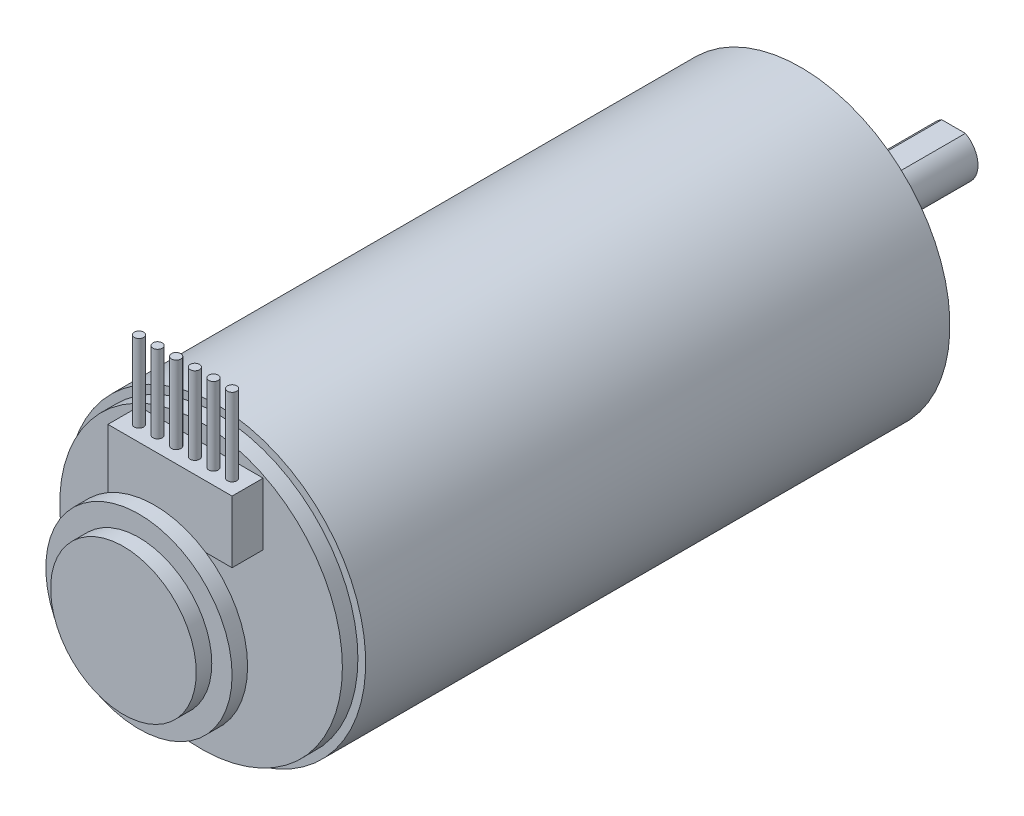
SolidWorks part; units mm, degrees
ref_plane "Front Plane" through (0, 0, 0) normal (0, 0, 1) x (1, 0, 0)
ref_plane "Top Plane" through (0, 0, 0) normal (0, 1, 0) x (1, 0, 0)
ref_plane "Right Plane" through (0, 0, 0) normal (1, 0, 0) x (0, 0, -1)
sketch "Sketch1" plane through (0, 0, 0) normal (0, 0, 1) x (1, 0, 0)
  circle A0 centre (0, 0) radius 2
  dimension "D1" = 4
extrude "Boss-Extrude1" add sketch "Sketch1" along normal blind 10
sketch "Sketch2" plane through (0, 0, 10) normal (0, 0, 1) x (1, 0, 0)
  circle A0 centre (0, 0) radius 3.5
  dimension "D1" = 7
extrude "Boss-Extrude2" add sketch "Sketch2" along normal blind 2.5
sketch "Sketch3" plane through (0, 0, 0) normal (0, 0, -1) x (-1, 0, 0)
  line L0 (0, 0) -> (0, 2) construction
  line L1 (-3.6247, 2.512) -> (3.6247, 2.512)
  line L2 (-3.6247, 2.512) -> (-3.6247, 1.75)
  line L3 (-3.6247, 1.75) -> (3.6247, 1.75)
  line L4 (3.6247, 2.512) -> (3.6247, 1.75)
  circle A1 centre (0, 0) radius 2 construction
  point P10 (0, 1.75)
  dimension "D1" = 1.75
  dimension "D2" = 0.762
  dimension "D3" = 3.6247
extrude "Cut-Extrude1" cut sketch "Sketch3" against normal blind 8
sketch "Sketch4" plane through (0, 0, 12.5) normal (0, 0, 1) x (1, 0, 0)
  circle A0 centre (0, 0) radius 12.2
  dimension "D1" = 24.4
extrude "Boss-Extrude3" add sketch "Sketch4" along normal blind 47.8
sketch "Sketch5" plane through (0, 0, 60.3) normal (0, 0, 1) x (1, 0, 0)
  circle A0 centre (0, 0) radius 11.565
  circle A1 centre (0, 0) radius 12.2 construction
  dimension "D1" = 0.635
extrude "Boss-Extrude4" add sketch "Sketch5" along normal blind 1.27
sketch "Sketch6" plane through (0, 0, 0) normal (0, 1, 0) x (1, 0, 0)
  line L0 (-11.565, -61.57) -> (11.565, -61.57) construction
  line L1 (-11.565, -61.57) -> (11.565, -61.57) construction
  line L3 (-5.08, -61.57) -> (5.08, -61.57)
  line L4 (-5.08, -61.57) -> (-5.08, -64.11)
  line L5 (-5.08, -64.11) -> (5.08, -64.11)
  line L6 (5.08, -61.57) -> (5.08, -64.11)
  point P6 (0, -61.57)
  point P7 (0, -61.57)
  point P8 (0, -61.57)
  dimension "D1" = 2.54
  dimension "D2" = 5.08
  dimension "D3" = 5.08
  dimension "D4" = 5.08
  dimension "D5" = 5.08
extrude "Boss-Extrude5" add sketch "Sketch6" along normal blind 5.08 from offset 5.08
sketch "Sketch8" plane through (0, 0, 61.57) normal (0, 0, 1) x (1, 0, 0)
  circle A0 centre (0, 0) radius 1.27
  dimension "D1" = 2.54
extrude "Boss-Extrude8" add sketch "Sketch8" along normal blind 3.81
sketch "Sketch9" plane through (0, 0, 65.38) normal (0, 0, 1) x (1, 0, 0)
  circle A0 centre (0, 0) radius 7.62
  dimension "D1" = 15.24
extrude "Boss-Extrude9" add sketch "Sketch9" along normal blind 1.27
sketch "Sketch10" plane through (0, 0, 66.65) normal (0, 0, 1) x (1, 0, 0)
  circle A0 centre (0, 0) radius 5.9577
extrude "Boss-Extrude10" add sketch "Sketch10" along normal blind 1.27
sketch "Sketch11" plane through (0, 10.16, 0) normal (0, 1, 0) x (1, 0, 0)
  line L0 (-5.08, -62.84) -> (5.08, -62.84) construction
  line L1 (-5.08, -61.57) -> (-5.08, -64.11) construction
  line L2 (5.08, -64.11) -> (5.08, -61.57) construction
  line L3 (0, -62.84) -> (-2.0643, -62.84) construction
  line L4 (-2.0643, -62.84) -> (-4.2233, -62.84) construction
  line L5 (0, -62.84) -> (2.159, -62.84) construction
  line L6 (2.159, -62.84) -> (4.318, -62.84) construction
  line L7 (0, -61.57) -> (0, -64.11) construction
  line L8 (5.08, -61.57) -> (-5.08, -61.57) construction
  line L9 (-5.08, -64.11) -> (5.08, -64.11) construction
  circle A0 centre (-0.762, -62.84) radius 0.381
  circle A1 centre (-2.286, -62.84) radius 0.381
  circle A2 centre (-3.81, -62.84) radius 0.381
  circle A3 centre (0.762, -62.84) radius 0.381
  circle A4 centre (2.286, -62.84) radius 0.381
  circle A5 centre (3.81, -62.84) radius 0.381
  dimension "D5" = 1.524
  dimension "D6" = 1.524
  dimension "D7" = 0.762
  dimension "D8" = 0.762
  dimension "D9" = 0.762
  dimension "D1" = 0.762
  dimension "D2" = 0.762
  dimension "D3" = 0.762
  dimension "D4" = 0.762
  dimension "D10" = 0.762
  dimension "D11" = 1.524
  dimension "D12" = 1.524
extrude "Boss-Extrude12" add sketch "Sketch11" along normal blind 6.35
equation "\"D2@Sketch11\"=\"D1@Sketch11\""
equation "\"D3@Sketch11\"=\"D1@Sketch11\""
equation "\"D5@Sketch11\"=2*\"D4@Sketch11\""
equation "\"D6@Sketch11\"=2*\"D4@Sketch11\""
equation "\"D7@Sketch11\"=\"D1@Sketch11\""
equation "\"D8@Sketch11\"=\"D1@Sketch11\""
equation "\"D9@Sketch11\"=\"D1@Sketch11\""
equation "\"D10@Sketch11\"=\"D4@Sketch11\""
equation "\"D11@Sketch11\"=\"D4@Sketch11\"*2"
equation "\"D12@Sketch11\"=2*\"D4@Sketch11\""
